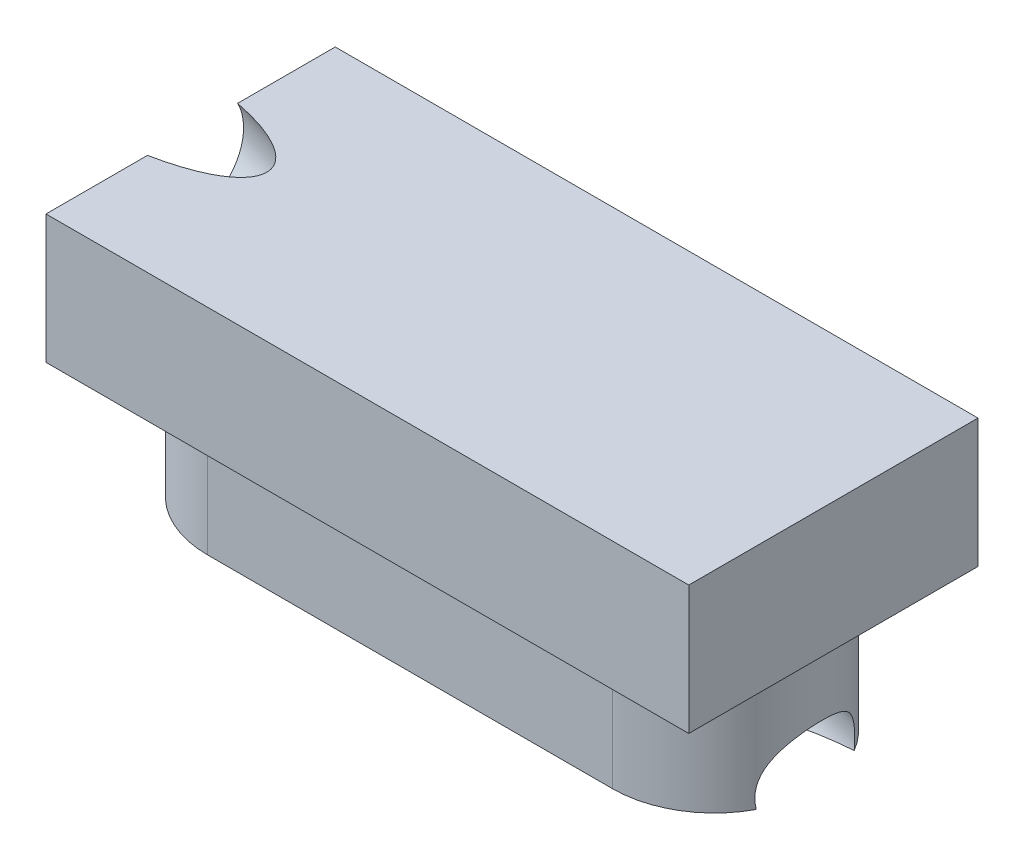
SolidWorks part; units mm, degrees
ref_plane "Front Plane" through (0, 0, 0) normal (0, 0, 1) x (1, 0, 0)
ref_plane "Top Plane" through (0, 0, 0) normal (0, 1, 0) x (1, 0, 0)
ref_plane "Right Plane" through (0, 0, 0) normal (1, 0, 0) x (0, 0, -1)
sketch "Sketch1" plane through (0, 0, 0) normal (0, 1, 0) x (1, 0, 0)
  line L0 (0, 1.3786) -> (0, -1.4577) construction
  line L1 (-1.575, 0.7464) -> (1.575, 0.7464)
  line L2 (-1.575, -0.8411) -> (1.575, -0.8411)
  line L3 (-1.575, -0.8411) -> (-1.575, 0.7464) construction
  line L4 (1.575, 0.7464) -> (1.575, -0.8411) construction
  arc A0 (-1.575, -0.8411) -> (-1.575, 0.7464) centre (-1.575, -0.0474) cw
  arc A1 (1.575, 0.7464) -> (1.575, -0.8411) centre (1.575, -0.0474) cw
  point P8 (0, 0.7464)
  dimension "D1" = 1.5875
  dimension "D3" = 0.7937
  dimension "D2" = 3.15
extrude "Boss-Extrude1" add sketch "Sketch1" along normal blind 1
sketch "Sketch2" [suppressed] plane through (0, 0, 0) normal (0, 0, 1) x (1, 0, 0)
  line L1 (1.575, 0) -> (2.3688, 0) construction
  line L3 (2.3688, 0) -> (-4.5982, 2.5357)
  line L4 (1.575, 0) -> (2.3688, 0) construction
  dimension "D1" = 20
ref_plane "Plane1" [suppressed] through (-1.3856, 1, 0) normal (-1, 0, 0) x (0, 0, 1)
sketch "Sketch5" plane through (0, 1, 0) normal (0, 1, 0) x (1, 0, 0)
  line L0 (0, -0.8411) -> (0, -1.1724) construction
  line L1 (-2.5, 1.0776) -> (2.5, 1.0776)
  line L2 (-2.5, 1.0776) -> (-2.5, -1.1724)
  line L3 (-2.5, -1.1724) -> (2.5, -1.1724)
  line L4 (2.5, 1.0776) -> (2.5, -1.1724)
  line L5 (-1.0372, -0.0474) -> (-2.5, -0.0474) construction
  line L7 (2.5, 1.0776) -> (-2.5, -1.1724) construction
  line L8 (-1.575, -0.8411) -> (1.575, -0.8411) construction
  line L9 (-1.575, 0.7464) -> (1.575, 0.7464) construction
  line L10 (-1.575, -0.8411) -> (1.575, -0.8411) construction
  line L11 (-1.575, 0.7464) -> (1.575, 0.7464) construction
  line L12 (-1.575, -0.8411) -> (1.575, -0.8411) construction
  line L13 (1.575, 0.7464) -> (-1.575, -0.8411) construction
  point P15 (0, -0.0474)
  point P17 (0, -0.0474)
  dimension "D1" = 2.25
  dimension "D2" = 5
extrude "Boss-Extrude2" add sketch "Sketch5" along normal blind 1
sketch "Sketch4" plane through (2.5, 1, 0) normal (-1, 0, 0) x (0, 0, 1)
  line L0 (0.0474, 0) -> (0, -3.1672) construction
  line L1 (1.1724, 0) -> (-1.0776, 0) construction
  circle A0 centre (0.0323, -1.0065) radius 0.3969
  point P3 (0.0323, -1.0065)
  dimension "D1" = 0.7937
sweep "Cut-Sweep3" [suppressed] cut profiles "Sketch4" path "Sketch2"
sketch "Sketch6" plane through (0, 0, 0) normal (0, 0, 1) x (1, 0, 0)
  line L0 (2.5, 0) -> (-2.8676, 1.9537)
  line L1 (1.575, 0) -> (2.3688, 0) construction
  line L2 (1.575, 0) -> (2.3688, 0) construction
  line L3 (2.5, 2) -> (-2.5, 2) construction
  line L4 (2.5, 2) -> (-2.5, 2) construction
  line L5 (2.5, 2) -> (2.5, 0) construction
  dimension "D1" = 20
sweep "Cut-Sweep4" cut profiles "Sketch4<2>" path "Sketch6"
sketch "Sketch4<2>" plane through (2.5, 1, 0) normal (-1, 0, 0) x (0, 0, 1) same geometry as "Sketch4"
